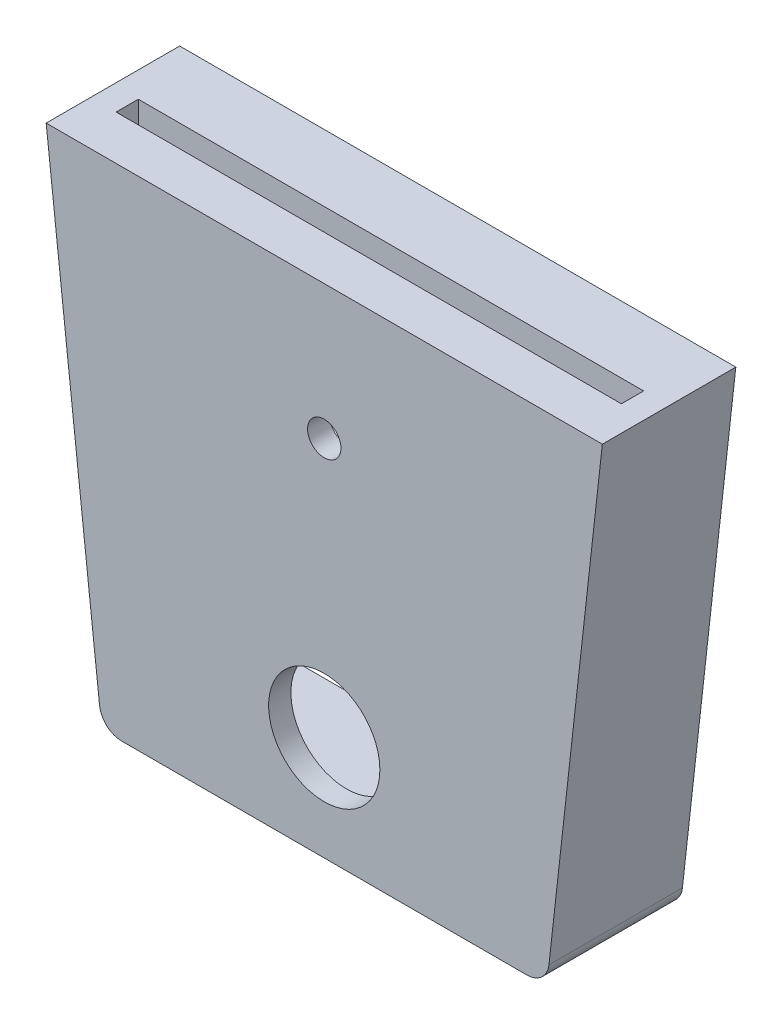
SolidWorks part; units mm, degrees
ref_plane "Front Plane" through (0, 0, 0) normal (0, 0, 1) x (1, 0, 0)
ref_plane "Top Plane" through (0, 0, 0) normal (0, 1, 0) x (1, 0, 0)
ref_plane "Right Plane" through (0, 0, 0) normal (1, 0, 0) x (0, 0, -1)
sketch "Sketch1" plane through (0, 0, 0) normal (0, 0, 1) x (1, 0, 0)
  line L0 (0, 56.7961) -> (0, -56.7961) construction
  line L1 (63.5, 56.7961) -> (-63.5, 56.7961)
  line L2 (-63.5, 56.7961) -> (-51.3049, -52.2806)
  line L3 (-46.2563, -56.7961) -> (46.2563, -56.7961)
  line L4 (63.5, 56.7961) -> (51.3049, -52.2806)
  arc A0 (-51.3049, -52.2806) -> (-46.2563, -56.7961) centre (-46.2563, -51.7161) ccw
  arc A1 (51.3049, -52.2806) -> (46.2563, -56.7961) centre (46.2563, -51.7161) cw
  circle A2 centre (0, 26.1693) radius 3.81
  circle A3 centre (0, -32.9791) radius 12.7
  point P10 (-50.8, -56.7961)
  dimension "D4" = 5.08
  dimension "D6" = 7.62
  dimension "D7" = 25.4
  dimension "D8" = 30.6268
  dimension "D9" = 23.8171
  dimension "D1" = 50.8
  dimension "D2" = 63.5
  dimension "D3" = 56.7961
  dimension "D5" = 109.0767
extrude "Boss-Extrude1" add sketch "Sketch1" against normal blind 5.08
sketch "Sketch2" plane through (0, 0, -5.08) normal (0, 0, 1) x (1, 0, 0)
  line L0 (0, 56.7961) -> (0, -56.7961) construction
  line L1 (63.5, 56.7961) -> (-63.5, 56.7961)
  line L2 (-63.5, 56.7961) -> (-51.3049, -52.2806)
  line L3 (-46.2563, -56.7961) -> (46.2563, -56.7961)
  line L4 (63.5, 56.7961) -> (51.3049, -52.2806)
  line L5 (-46.2563, -56.7961) -> (46.2563, -56.7961) construction
  line L6 (-57.8204, 51.7161) -> (57.8204, 51.7161)
  line L7 (57.8204, 51.7161) -> (46.7612, -47.2006)
  line L8 (41.7126, -51.7161) -> (-41.7126, -51.7161)
  line L9 (-57.8204, 51.7161) -> (-46.7612, -47.2006)
  arc A0 (-51.3049, -52.2806) -> (-46.2563, -56.7961) centre (-46.2563, -51.7161) ccw
  arc A1 (51.3049, -52.2806) -> (46.2563, -56.7961) centre (46.2563, -51.7161) cw
  circle A2 centre (0, 26.1693) radius 3.81
  circle A3 centre (0, -32.9791) radius 12.7
  arc A4 (46.7612, -47.2006) -> (41.7126, -51.7161) centre (41.7126, -46.6361) cw
  arc A5 (-46.7612, -47.2006) -> (-41.7126, -51.7161) centre (-41.7126, -46.6361) ccw
  point P10 (-50.8, -56.7961)
  point P27 (0, -51.7161)
  point P28 (0, 51.7161)
  arc M12 (51.3049, -52.2806) -> (46.2563, -56.7961) centre (46.2563, -51.7161) cw
  line M13 (46.2563, -56.7961) -> (-46.2563, -56.7961)
  arc M14 (-46.2563, -56.7961) -> (-51.3049, -52.2806) centre (-46.2563, -51.7161) cw
  line M15 (-51.3049, -52.2806) -> (-63.5, 56.7961)
  line M16 (-63.5, 56.7961) -> (63.5, 56.7961)
  line M17 (63.5, 56.7961) -> (51.3049, -52.2806)
  dimension "D4" = 5.08
  dimension "D6" = 7.62
  dimension "D7" = 25.4
  dimension "D8" = 30.6268
  dimension "D9" = 23.8171
  dimension "D11" = 5.08
  dimension "D1" = 50.8
  dimension "D2" = 63.5
  dimension "D3" = 5.08
  dimension "D5" = 109.0767
  dimension "D10" = 0
extrude "Boss-Extrude2" add sketch "Sketch2" against normal blind 25.4 contours L0 L1 L8 A4 L7 L6 M17 M12 M13 | L0 L6 L9 A5 L8 L3 M16 M14 M15 region at (31.75, 55.4948, -5.08) region at (-1.3014, 54.2561, -5.08)
sketch "Sketch3" plane through (0, 56.7961, 0) normal (0, 1, 0) x (1, 0, 0)
  line L0 (57.6928, 10.16) -> (57.6928, 15.24)
  line L1 (57.6928, 10.16) -> (-57.6928, 10.16)
  line L2 (57.6928, 15.24) -> (-57.6928, 15.24)
  line L3 (-57.6928, 10.16) -> (-57.6928, 15.24)
  line L6 (63.5, 0) -> (-63.5, 0) construction
  line L8 (-63.5, 30.48) -> (-63.5, 0) construction
  dimension "D1" = 115.3856
  dimension "D2" = 5.8072
  dimension "D3" = 10.16
  dimension "D4" = 5.08
extrude "Cut-Extrude2" cut sketch "Sketch3" against normal blind 6.35
sketch "Sketch4" plane through (0, 0, -30.48) normal (0, 0, -1) x (-1, 0, 0)
  line L0 (0, 51.7161) -> (0, -51.7161) construction
  line L1 (57.8204, 51.7161) -> (-57.8204, 51.7161) construction
  line L2 (-41.7126, -51.7161) -> (41.7126, -51.7161) construction
  line L3 (-52.9958, 8.564) -> (-33.9458, 8.564)
  line L4 (-57.8204, 51.7161) -> (-46.7612, -47.2006) construction
  line L5 (-33.9458, 8.564) -> (-33.9458, -4.136)
  line L6 (-33.9458, -4.136) -> (-51.5759, -4.136)
  line L7 (-57.8204, 51.7161) -> (-46.7612, -47.2006) construction
  line L8 (33.9458, -4.136) -> (51.5759, -4.136)
  line L9 (33.9458, 8.564) -> (33.9458, -4.136)
  line L10 (52.9958, 8.564) -> (33.9458, 8.564)
  line L11 (-51.5759, -4.136) -> (-52.9958, 8.564)
  line L12 (52.9958, 8.564) -> (51.5759, -4.136)
  dimension "D1" = 19.05
  dimension "D2" = 12.7
  dimension "D3" = 33.9458
extrude "Boss-Extrude3" add sketch "Sketch4" against normal blind 2.54
sketch "Sketch5" plane through (0, 0, -30.48) normal (0, 0, -1) x (-1, 0, 0)
  line L0 (-43.4708, 8.564) -> (-42.7609, -4.136) construction
  line L1 (-33.9458, 8.564) -> (-52.9958, 8.564) construction
  line L2 (-51.5759, -4.136) -> (-33.9458, -4.136) construction
  line L3 (0, 51.7161) -> (0, -51.7161) construction
  line L4 (57.8204, 51.7161) -> (-57.8204, 51.7161) construction
  line L5 (-41.7126, -51.7161) -> (41.7126, -51.7161) construction
  circle A0 centre (-43.1159, 2.214) radius 1.905
  circle A1 centre (43.1159, 2.214) radius 1.905
  dimension "D1" = 3.81
extrude "Cut-Extrude3" cut sketch "Sketch5" against normal blind 2.54
